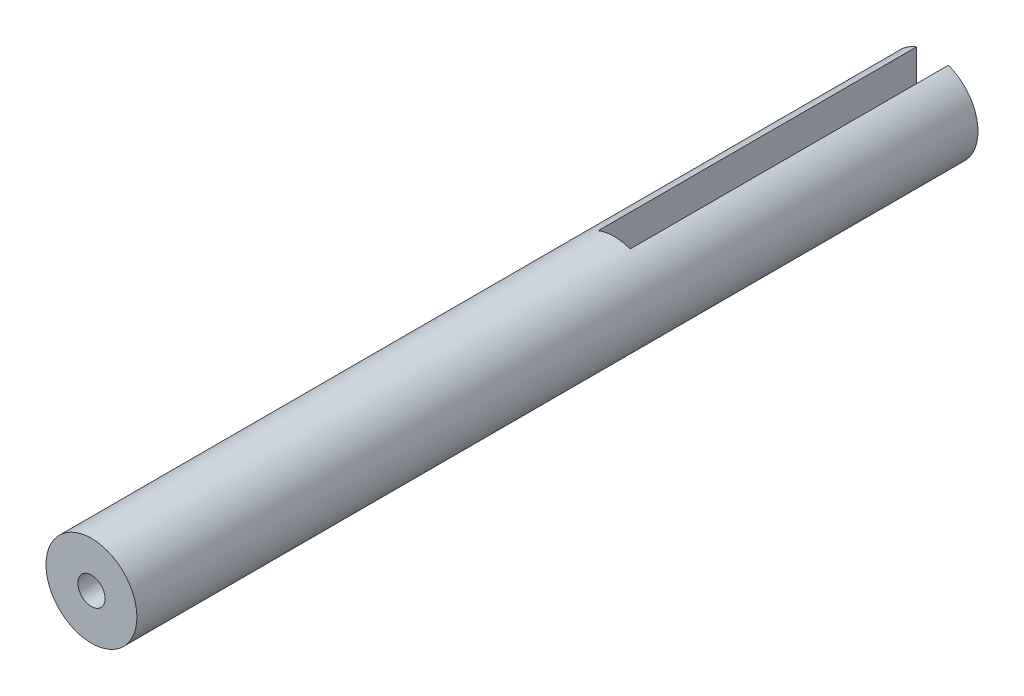
SolidWorks part; units mm, degrees
ref_plane "Front Plane" through (0, 0, 0) normal (0, 0, 1) x (1, 0, 0)
ref_plane "Top Plane" through (0, 0, 0) normal (0, 1, 0) x (1, 0, 0)
ref_plane "Right Plane" through (0, 0, 0) normal (1, 0, 0) x (0, 0, -1)
sketch "Sketch1" plane through (0, 0, 0) normal (0, 0, 1) x (1, 0, 0)
  line L1 (3.5, 11.9571) -> (-3.5, 11.9571)
  line L2 (3.5, 11.9571) -> (3.5, -11.9571)
  line L3 (3.5, -11.9571) -> (-3.5, -11.9571)
  line L4 (-3.5, 11.9571) -> (-3.5, -11.9571)
  line L5 (3.5, 11.9571) -> (-3.5, -11.9571) construction
  line L6 (3.5, -11.9571) -> (-3.5, 11.9571) construction
  circle A0 centre (0, 0) radius 10
  dimension "D1" = 20
  dimension "D2" = 7
extrude "Boss-Extrude1" add sketch "Sketch1" along normal blind 185 contours A0
sketch "Sketch2" plane through (0, 0, 0) normal (0, 0, -1) x (-1, 0, 0)
extrude "Cut-Extrude1" cut sketch "Sketch1<3>" along normal blind 70 contours L2 A0 L4 region at (0, 0, 0)
sketch "Sketch1<3>" plane through (0, 0, 0) normal (0, 0, 1) x (1, 0, 0) same geometry as "Sketch1"
sketch "Sketch3" plane through (0, 0, 185) normal (0, 0, 1) x (1, 0, 0)
  circle A0 centre (0, 0) radius 3
  dimension "D1" = 6
extrude "Cut-Extrude2" cut sketch "Sketch3" against normal blind 20
